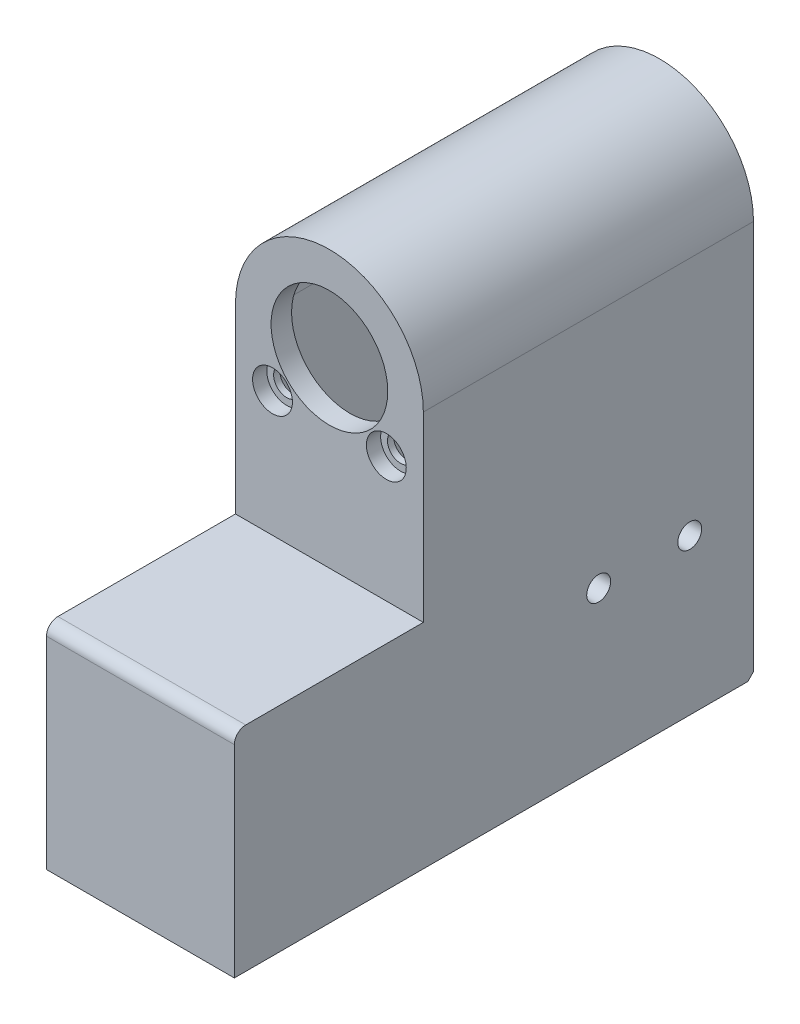
SolidWorks part; units mm, degrees
ref_plane "Front Plane" through (0, 0, 0) normal (0, 0, 1) x (1, 0, 0)
ref_plane "Top Plane" through (0, 0, 0) normal (0, 1, 0) x (1, 0, 0)
ref_plane "Right Plane" through (0, 0, 0) normal (1, 0, 0) x (0, 0, -1)
sketch "Sketch1" plane through (0, 0, 0) normal (0, 0, 1) x (1, 0, 0)
  line L0 (0, 0) -> (33, 0)
  line L1 (16.5, 0) -> (29, 0)
  line L2 (16.5, 0) -> (16.5, 9.4766)
  line L3 (4, 0) -> (4, 80.5)
  line L4 (29, 0) -> (29, 80.5)
  line L5 (0, 0) -> (0, 80.5)
  line L6 (0, 80.5) -> (4, 80.5)
  line L7 (33, 0) -> (33, 80.5)
  line L8 (33, 80.5) -> (29, 80.5)
  arc A0 (33, 80.5) -> (0, 80.5) centre (16.5, 80.5) ccw
  arc A1 (4, 80.5) -> (29, 80.5) centre (16.5, 80.5) cw
  point P5 (4, 0)
  dimension "D1" = 33
  dimension "D2" = 12.5
  dimension "D3" = 80.5
extrude "Boss-Extrude1" add sketch "Sketch1" along normal blind 71 contours L6 L5 L0 L3 | L6 A1 L8 A0 | L7 L8 L4 L0 region at (2, 40.25, 0) region at (16.5, 96.631, 0) region at (31, 40.25, 0)
sketch "Sketch2" plane through (0, 0, 71) normal (0, 0, 1) x (1, 0, 0)
  line L2 (33, 48.5) -> (0, 48.5)
  line L3 (0, 0) -> (0, 80.5) construction
  line L4 (0, 48.5) -> (0, 80.5)
  line L5 (33, 0) -> (33, 80.5) construction
  line L6 (33, 48.5) -> (33, 80.5)
  arc A0 (33, 80.5) -> (0, 80.5) centre (16.5, 80.5) ccw construction
  arc A1 (33, 80.5) -> (0, 80.5) centre (16.5, 80.5) ccw
  point P8 (16.5, 48.5)
extrude "Boss-Extrude2" add sketch "Sketch2" against normal blind 4
sketch "Sketch3" plane through (0, 0, 67) normal (0, 0, -1) x (-1, 0, 0)
  line L0 (-4, 48.5) -> (-29, 48.5) construction
  line L1 (-4, 48.5) -> (-29, 48.5)
  line L3 (-29, 44.5) -> (-4, 44.5)
  line L5 (0, 0) -> (0, 80.5) construction
  line L6 (0, 0) -> (0, 48.5)
  line L7 (-4, 48.5) -> (0, 48.5)
  line L8 (0, 0) -> (-3.8379, 0)
  line L9 (-4, 44.5) -> (-3.8379, 0)
  line L10 (-16.5, 44.5) -> (-16.5, 41.0104)
  line L11 (-33, 0) -> (-33, 48.5)
  line L12 (-29, 48.5) -> (-33, 48.5)
  line L13 (-29, 44.5) -> (-29.1621, 0)
  line L14 (-33, 0) -> (-29.1621, 0)
  line M8 (-29, 48.5) -> (-4, 48.5)
extrude "Boss-Extrude3" add sketch "Sketch3" against normal blind 34.2 contours L11 L14 L13 L3 L9 L8 L6 L7 L12 M8 region at (2, 47.9134, 67)
sketch "Sketch4" plane through (0, 0, 0) normal (0, 0, -1) x (-1, 0, 0)
  line L6 (-4, 80.5) -> (-4, 0)
  line L7 (-4, 0) -> (0, 0)
  line L8 (0, 0) -> (0, 80.5)
  line L9 (-33, 80.5) -> (-33, 0)
  line L10 (-33, 0) -> (-29, 0)
  line L11 (-29, 0) -> (-29, 80.5)
  line L12 (-4, 80.5) -> (-4, 0)
  line L13 (-4, 0) -> (0, 0)
  line L14 (0, 0) -> (0, 80.5)
  line L15 (-33, 80.5) -> (-33, 0)
  line L16 (-33, 0) -> (-29, 0)
  line L17 (-29, 0) -> (-29, 80.5)
  arc A2 (0, 80.5) -> (-33, 80.5) centre (-16.5, 80.5) ccw
  arc A3 (-4, 80.5) -> (-29, 80.5) centre (-16.5, 80.5) ccw
  arc A4 (0, 80.5) -> (-33, 80.5) centre (-16.5, 80.5) ccw
  arc A5 (-4, 80.5) -> (-29, 80.5) centre (-16.5, 80.5) ccw
  dimension "D1" = 0
extrude "Cut-Extrude1" cut sketch "Sketch4" against normal blind 13
sketch "Sketch5" plane through (0, 0, 71) normal (0, 0, 1) x (1, 0, 0)
  line L0 (0, 80.5) -> (33, 80.5)
  circle A0 centre (16.5, 80.5) radius 10
  dimension "D1" = 20
extrude "Cut-Extrude2" cut sketch "Sketch5" against normal blind 13 contours L0 A0 | L0 A0 region at (16.5, 84.7441, 71) region at (16.5, 76.2559, 71)
sketch "Sketch6" plane through (0, 0, 71) normal (0, 0, 1) x (1, 0, 0)
  line L0 (16.5, 70.5) -> (16.5, 73.1374)
  line L1 (16.5, 70.5) -> (33, 70.5)
  line L2 (33, 48.5) -> (33, 80.5) construction
  circle A0 centre (26.5, 70.5) radius 1.7
  circle A1 centre (6.5, 70.5) radius 1.7
  dimension "D2" = 3.4
  dimension "D1" = 6.5
extrude "Cut-Extrude3" cut sketch "Sketch6" against normal blind 13 contours A1 | L1 A0 | L1 A0 region at (26.5, 71.2215, 71) region at (26.5, 69.7785, 71) region at (6.5, 70.5, 71)
sketch "Sketch7" plane through (0, 0, 71) normal (0, 0, 1) x (1, 0, 0)
  circle A0 centre (6.5, 70.5) radius 3.25
  circle A1 centre (26.5, 70.5) radius 3.25
  dimension "D1" = 6.5
extrude "Cut-Extrude4" cut sketch "Sketch7" against normal blind 2.5
sketch "Sketch9" plane through (0, 0, 0) normal (0, -1, 0) x (1, 0, 0)
  line L0 (29.1621, 101.2) -> (29.1621, 71) construction
  line L1 (29.1621, 101.2) -> (29.1621, 71)
  line L2 (29.1621, 71) -> (29, 71)
  line L3 (29, 71) -> (29, 120)
  line L4 (29, 120) -> (29.1621, 101.2)
  line L6 (29, 67) -> (4, 67) construction
  line L7 (29, 67) -> (4, 67)
  line L8 (16.5, 67) -> (16.5, 71)
  line L9 (4, 120) -> (3.8379, 101.2)
  line L10 (4, 71) -> (4, 120)
  line L11 (3.8379, 71) -> (4, 71)
  line L12 (3.8379, 101.2) -> (3.8379, 71)
extrude "Boss-Extrude4" add sketch "Sketch9" against normal up to surface (44.5 mm away) contours L4 L1 L2 L3 | L9 L12 L11 L10 up to face at (16.5, 44.5, 79.7333)
sketch "Sketch10" plane through (0, 0, 101.2) normal (0, 0, 1) x (1, 0, 0)
  line L1 (40.2439, -6.5645) -> (-5.7585, -6.5645)
  line L2 (40.2439, -6.5645) -> (40.2439, 55.1467)
  line L3 (40.2439, 55.1467) -> (-5.7585, 55.1467)
  line L4 (-5.7585, -6.5645) -> (-5.7585, 55.1467)
  line L5 (40.2439, -6.5645) -> (-5.7585, 55.1467) construction
  line L6 (40.2439, 55.1467) -> (-5.7585, -6.5645) construction
  point P0 (17.2427, 24.2911)
extrude "Cut-Extrude5" cut sketch "Sketch10" along normal blind 42
sketch "Sketch11" plane through (0, 0, 101.2) normal (0, 0, 1) x (1, 0, 0)
  line L0 (29, 0) -> (4, 0)
  line L8 (4, 44.5) -> (29, 44.5)
  line L9 (29, 44.5) -> (29, 0)
  line L10 (29, 0) -> (33, 0)
  line L11 (33, 0) -> (33, 48.5)
  line L12 (33, 48.5) -> (0, 48.5)
  line L13 (0, 48.5) -> (0, 0)
  line L14 (0, 0) -> (4, 0)
  line L15 (4, 0) -> (4, 44.5)
  line L18 (29, 0) -> (33, 0)
  line L19 (33, 0) -> (33, 48.5)
  line L20 (33, 48.5) -> (0, 48.5)
  line L21 (0, 48.5) -> (0, 0)
  line L22 (0, 0) -> (4, 0)
  dimension "D1" = 0
extrude "Boss-Extrude5" add sketch "Sketch11" along normal blind 4
sketch "Sketch12" plane through (0, 0, 0) normal (0, -1, 0) x (1, 0, 0)
  line L8 (4, 13) -> (4, 101.2)
  line L9 (4, 101.2) -> (29, 101.2)
  line L10 (29, 101.2) -> (29, 13)
  line L11 (29, 13) -> (33, 13)
  line L12 (33, 13) -> (33, 105.2)
  line L13 (33, 105.2) -> (0, 105.2)
  line L14 (0, 105.2) -> (0, 13)
  line L15 (0, 13) -> (4, 13)
  line L16 (4, 13) -> (4, 101.2)
  line L17 (4, 101.2) -> (29, 101.2)
  line L18 (29, 101.2) -> (29, 13)
  line L19 (29, 13) -> (33, 13)
  line L20 (33, 13) -> (33, 105.2)
  line L21 (33, 105.2) -> (0, 105.2)
  line L22 (0, 105.2) -> (0, 13)
  line L23 (0, 13) -> (4, 13)
  dimension "D1" = 0
extrude "Cut-Extrude6" cut sketch "Sketch12" against normal blind 10.6
sketch "Sketch13" plane through (0, 0, 0) normal (-1, 0, 0) x (0, 0, 1)
  line L0 (105.2, 10.6) -> (13, 10.6) construction
  line L1 (13, 10.6) -> (13, 80.5) construction
  circle A0 centre (40.2, 38.3) radius 1.9
  circle A1 centre (24.2, 38.3) radius 1.9
  dimension "D1" = 27.7
  dimension "D2" = 3.8
  dimension "D3" = 27.2
  dimension "D4" = 16
extrude "Cut-Extrude7" cut sketch "Sketch13" against normal up to surface (33 mm away) contours A1 | A0 up to face at (33, 46.5333, 63.0667)
sketch "Sketch14" plane through (0, 0, 101.2) normal (0, 0, -1) x (-1, 0, 0)
  line L4 (-29, 10.6) -> (-4, 10.6)
  line L5 (-4, 10.6) -> (-4, 44.5)
  line L6 (-4, 44.5) -> (-29, 44.5)
  line L7 (-29, 44.5) -> (-29, 10.6)
  line L8 (-29, 10.6) -> (-4, 10.6)
  line L9 (-4, 10.6) -> (-4, 44.5)
  line L10 (-4, 44.5) -> (-29, 44.5)
  line L11 (-29, 44.5) -> (-29, 10.6)
  dimension "D1" = 0
extrude "Boss-Extrude6" add sketch "Sketch14" along normal blind 1
sketch "Sketch15" plane through (0, 10.6, 0) normal (0, -1, 0) x (1, 0, 0)
  line L0 (29, 100.2) -> (4, 100.2) construction
  line L1 (29, 100.2) -> (4, 100.2)
  line L2 (16.5, 100.2) -> (16.5, 101.5)
  line L3 (16.5, 105.2) -> (16.5, 103.9)
  line L4 (33, 105.2) -> (0, 105.2) construction
  line L5 (16.5, 101.5) -> (6.3, 101.5)
  line L6 (16.5, 101.5) -> (26.7, 101.5)
  line L7 (26.7, 101.5) -> (26.7, 103.9)
  line L8 (26.7, 103.9) -> (6.3, 103.9)
  line L9 (6.3, 103.9) -> (6.3, 101.5)
  dimension "D1" = 1.3
  dimension "D2" = 1.3
  dimension "D3" = 10.2
  dimension "D4" = 10.2
extrude "Cut-Extrude8" cut sketch "Sketch15" against normal blind 15 contours L8 L9 L5 L6 L7 region at (16.5, 10.6, 102.7)
sketch "Sketch16" plane through (0, 10.6, 0) normal (0, -1, 0) x (1, 0, 0)
  line L1 (26.7, 103.9) -> (6.3, 103.9) construction
  line L3 (21.7, 103.9) -> (21.7, 105.2)
  line L4 (33, 105.2) -> (0, 105.2) construction
  line L5 (21.7, 105.2) -> (11.3, 105.2)
  line L6 (11.3, 105.2) -> (11.3, 103.9)
  line L7 (21.7, 103.9) -> (11.3, 103.9)
  point P0 (16.5, 103.9)
  point P2 (16.5, 105.2)
  dimension "D1" = 10.4
extrude "Cut-Extrude9" cut sketch "Sketch16" against normal up to surface (15 mm away) up to face at (16.5, 25.6, 102.7)
sketch "Sketch17" plane through (0, 25.6, 0) normal (0, -1, 0) x (1, 0, 0)
  line L8 (26.7, 103.9) -> (21.7, 103.9)
  line L9 (21.7, 103.9) -> (21.7, 105.2)
  line L10 (21.7, 105.2) -> (11.3, 105.2)
  line L11 (11.3, 105.2) -> (11.3, 103.9)
  line L12 (11.3, 103.9) -> (6.3, 103.9)
  line L13 (6.3, 103.9) -> (6.3, 101.5)
  line L14 (6.3, 101.5) -> (26.7, 101.5)
  line L15 (26.7, 101.5) -> (26.7, 103.9)
  line L16 (26.7, 103.9) -> (21.7, 103.9)
  line L17 (21.7, 103.9) -> (21.7, 105.2)
  line L18 (21.7, 105.2) -> (11.3, 105.2)
  line L19 (11.3, 105.2) -> (11.3, 103.9)
  line L20 (11.3, 103.9) -> (6.3, 103.9)
  line L21 (6.3, 103.9) -> (6.3, 101.5)
  line L22 (6.3, 101.5) -> (26.7, 101.5)
  line L23 (26.7, 101.5) -> (26.7, 103.9)
  dimension "D1" = 0
extrude "popunio rupu" add sketch "Sketch17" along normal up to surface (15 mm away) up to face at (16.5, 10.6, 80.7375)
sketch "Sketch18" plane through (0, 0, 105.2) normal (0, 0, 1) x (1, 0, 0)
  line L4 (0, 48.5) -> (0, 10.6)
  line L5 (0, 10.6) -> (33, 10.6)
  line L6 (33, 10.6) -> (33, 48.5)
  line L7 (33, 48.5) -> (0, 48.5)
  line L8 (0, 48.5) -> (0, 10.6)
  line L9 (0, 10.6) -> (33, 10.6)
  line L10 (33, 10.6) -> (33, 48.5)
  line L11 (33, 48.5) -> (0, 48.5)
  dimension "D1" = 0
extrude "sasekao za jedan mm" cut sketch "Sketch18" against normal blind 1
fillet "Fillet1" radius 2 1 edges at (16.5, 48.5, 104.2)
sketch "Sketch19" plane through (0, 0, 71) normal (0, 0, 1) x (1, 0, 0)
  circle A0 centre (6.5, 70.5) radius 3.25 construction
  circle A1 centre (6.5, 70.5) radius 3.25
  circle A2 centre (6.5, 70.5) radius 3.5
  circle A4 centre (26.5, 70.5) radius 3.5
  dimension "D1" = 7
extrude "pove'ao rupe za zavrtnje" cut sketch "Sketch19" against normal up to surface (2.5 mm away) up to face at (8.2, 70.5, 68.5)
sketch "Sketch20" plane through (0, 10.6, 0) normal (0, -1, 0) x (1, 0, 0)
  line L8 (33, 13) -> (33, 104.2)
  line L9 (33, 104.2) -> (0, 104.2)
  line L10 (0, 104.2) -> (0, 13)
  line L11 (0, 13) -> (4, 13)
  line L12 (4, 13) -> (4, 100.2)
  line L13 (4, 100.2) -> (29, 100.2)
  line L14 (29, 100.2) -> (29, 13)
  line L15 (29, 13) -> (33, 13)
  line L16 (33, 13) -> (33, 104.2)
  line L17 (33, 104.2) -> (0, 104.2)
  line L18 (0, 104.2) -> (0, 13)
  line L19 (0, 13) -> (4, 13)
  line L20 (4, 13) -> (4, 100.2)
  line L21 (4, 100.2) -> (29, 100.2)
  line L22 (29, 100.2) -> (29, 13)
  line L23 (29, 13) -> (33, 13)
  dimension "D1" = 0
extrude "skratio dno" cut sketch "Sketch20" against normal blind 0.4
sketch "Sketch21" plane through (0, 44.5, 0) normal (0, -1, 0) x (1, 0, 0)
  line L4 (29, 100.2) -> (4, 100.2)
  line L5 (4, 100.2) -> (4, 67)
  line L6 (4, 67) -> (29, 67)
  line L7 (29, 67) -> (29, 100.2)
  line L8 (29, 100.2) -> (4, 100.2)
  line L9 (4, 100.2) -> (4, 67)
  line L10 (4, 67) -> (29, 67)
  line L11 (29, 67) -> (29, 100.2)
  dimension "D1" = 0
extrude "napravio malo vi[e mesta za vrh razvodnika" cut sketch "Sketch21" against normal blind 0.4
sketch "Sketch22" plane through (0, 0, 67) normal (0, 0, -1) x (-1, 0, 0)
  line L3 (-29, 44.9) -> (-4, 44.9)
  line L4 (-4, 44.9) -> (-4, 80.5)
  line L5 (-29, 80.5) -> (-29, 44.9)
  line L6 (-29, 44.9) -> (-4, 44.9)
  line L7 (-4, 44.9) -> (-4, 80.5)
  line L8 (-29, 80.5) -> (-29, 44.9)
  arc A1 (-4, 80.5) -> (-29, 80.5) centre (-16.5, 80.5) ccw
  arc A2 (-4, 80.5) -> (-29, 80.5) centre (-16.5, 80.5) ccw
  dimension "D1" = 0
extrude "skratio ceoni deo" cut sketch "Sketch22" against normal blind 0.4
sketch "Sketch23" plane through (0, 0, 13) normal (0, 0, -1) x (-1, 0, 0)
  line L0 (-29, 80.5) -> (-29, 11)
  line L1 (-29, 11) -> (-29.2, 11)
  line L2 (-29.2, 11) -> (-29.2, 80.5)
  line L3 (-16.5, 80.5) -> (-16.5, 75.0754)
  line L4 (-4, 11) -> (-3.8, 11)
  line L5 (-3.8, 11) -> (-3.8, 80.5)
  line L6 (-4, 80.5) -> (-4, 11) construction
  line L7 (-4, 80.5) -> (-4, 11)
  arc A0 (-4, 80.5) -> (-29, 80.5) centre (-16.5, 80.5) ccw construction
  arc A1 (-4, 80.5) -> (-29, 80.5) centre (-16.5, 80.5) ccw
  arc A2 (-29.2, 80.5) -> (-3.8, 80.5) centre (-16.5, 80.5) cw
extrude "napravio mesta za drzac 1" cut sketch "Sketch23" against normal up to surface (54.4 mm away) contours L0 L1 L2 A2 L5 L4 L7 A1 up to face at (4.8, 70.5, 67.4)
sketch "Sketch24" plane through (0, 0, 67.4) normal (0, 0, -1) x (-1, 0, 0)
  line L0 (-3.8, 80.5) -> (-3.8, 11) construction
  line L1 (-3.8, 11) -> (-4, 11) construction
  line L2 (-4, 11) -> (-4, 44.9) construction
  line L3 (-29.2, 11) -> (-29, 11) construction
  line L4 (-29.2, 80.5) -> (-29.2, 11) construction
  line L5 (-29, 11) -> (-29, 44.9) construction
  line L6 (-3.8, 44.9) -> (-3.8, 11)
  line L7 (-3.8, 11) -> (-4, 11)
  line L8 (-4, 11) -> (-4, 44.9)
  line L9 (-29.2, 11) -> (-29, 11)
  line L10 (-29.2, 44.9) -> (-29.2, 11)
  line L11 (-29, 11) -> (-29, 44.9)
  line L12 (-29.2, 44.9) -> (-29, 44.9)
  line L13 (-4, 44.9) -> (-3.8, 44.9)
extrude "napravio emsta za drzac 2" cut sketch "Sketch24" against normal up to surface (32.8 mm away) up to face at (16.5, 27.95, 100.2)
chamfer "Chamfer1" distance 1 angle 45 2 edges at (1.9, 11, 13) (31.1, 11, 13)
sketch "Sketch25" plane through (0, 0, 0) normal (-1, 0, 0) x (0, 0, 1)
  circle A0 centre (24.2, 38.3) radius 2.1
  circle A1 centre (40.2, 38.3) radius 2.1
  dimension "D1" = 4.2
extrude "pove'ao otvore za razvodnik" cut sketch "Sketch25" against normal up to surface (33 mm away) up to face at (33, 38.3, 26.1)
sketch "Sketch26" plane through (0, 0, 68.5) normal (0, 0, 1) x (1, 0, 0)
  circle A0 centre (26.5, 70.5) radius 2.3
  circle A1 centre (6.5, 70.5) radius 2.3
  dimension "D1" = 4.6
  dimension "D2" = 4.6
extrude "povecao otvor za M3" cut sketch "Sketch26" against normal up to surface (1.1 mm away) up to face at (16.5, 65.875, 67.4)
sketch "Sketch27" plane through (0, 0, 71) normal (0, 0, 1) x (1, 0, 0)
  circle A0 centre (16.5, 80.5) radius 10.25
  dimension "D1" = 20.5
extrude "povecao otvor za prikljucak" cut sketch "Sketch27" against normal blind 10
